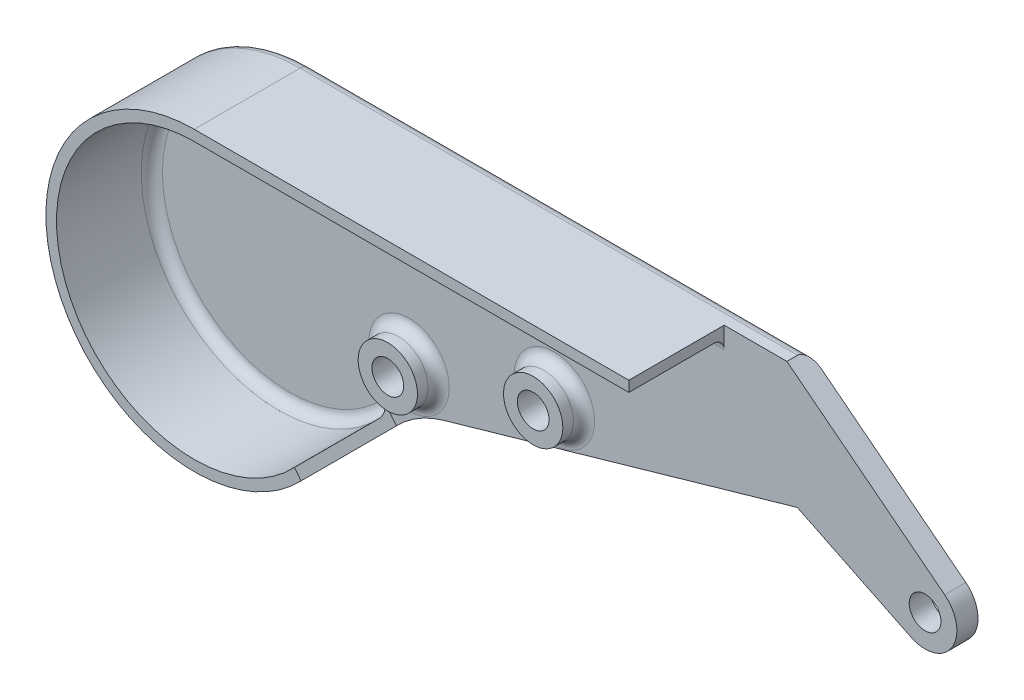
SolidWorks part; units mm, degrees
ref_plane "前视基准面" through (0, 0, 0) normal (0, 0, 1) x (1, 0, 0)
ref_plane "上视基准面" through (0, 0, 0) normal (0, 1, 0) x (1, 0, 0)
ref_plane "右视基准面" through (0, 0, 0) normal (1, 0, 0) x (0, 0, -1)
sketch "Sketch1" plane through (0, 0, 0) normal (0, 0, 1) x (1, 0, 0)
  line L0 (0, 14) -> (46.9536, 14)
  line L1 (46.9536, 14) -> (61.847, 2.364)
  line L2 (4.7883, -13.1557) -> (47.933, 2.5477) construction
  line L3 (47.933, 2.5477) -> (58.6849, -2.6964)
  line L4 (14.5376, -7.0283) -> (47.933, 2.5477)
  arc A0 (0, 14) -> (4.7883, -13.1557) centre (0, 0) ccw
  arc A1 (58.6849, -2.6964) -> (61.847, 2.364) centre (60, 0) ccw
  circle A2 centre (60, 0) radius 1.5
  arc A3 (4.7883, -13.1557) -> (10.0881, -9.7072) centre (0, 0) ccw
  circle A4 centre (0, 0) radius 4.5 construction
  arc A5 (14.5376, -7.0283) -> (10.0881, -9.7072) centre (17.2939, -16.6409) ccw
  dimension "D2" = 6
  dimension "D3" = 28
  dimension "D7" = 3
  dimension "D8" = 9
  dimension "D10" = 10
  dimension "D1" = 60
  dimension "D4" = 38
  dimension "D5" = 20
  dimension "D6" = 12
  dimension "D9" = 16
extrude "Boss-Extrude1" add sketch "Sketch1" along normal blind 2
sketch "Sketch2" plane through (0, 0, 0) normal (0, 0, -1) x (-1, 0, 0)
  line L1 (-46.9536, 14) -> (0, 14) construction
  line L3 (-41.0332, 14) -> (0, 14)
  line L4 (-41.0332, 13) -> (0, 13)
  line L6 (-41.0332, 13) -> (-41.0332, 14)
  line L8 (-10.0881, -9.7072) -> (-43.3043, 10.251) construction
  line L9 (-9.4573, -8.9196) -> (-42.7893, 11.1082) construction
  line L10 (-46.9536, 14) -> (0, 14) construction
  line L11 (-46.9536, 13) -> (0, 13) construction
  line L12 (-10.0881, -9.7072) -> (-9.4573, -8.9196)
  arc A0 (-10.0881, -9.7072) -> (0, 14) centre (0, 0) ccw construction
  arc A1 (-10.0881, -9.7072) -> (0, 14) centre (0, 0) ccw
  arc A2 (-9.4573, -8.9196) -> (0, 13) centre (0, 0) ccw
  dimension "D1" = 1
extrude "Boss-Extrude2" [suppressed] add sketch "Sketch2" along normal blind 9
fillet "Fillet1" [suppressed] radius 1
fillet "Fillet2" [suppressed] radius 1
sketch "Sketch3" plane through (0, 0, 0) normal (0, 0, -1) x (-1, 0, 0)
  line L0 (0, 0) -> (7.0202, 0) construction
  line L1 (-11.2763, -4.1042) -> (0, 0) construction
  circle A0 centre (-11.2763, -4.1042) radius 1.5
  circle A1 centre (-25, 0) radius 1.5
  circle A2 centre (-25, 0) radius 2.8
  circle A3 centre (-11.2763, -4.1042) radius 2.8
  dimension "D1" = 3
  dimension "D2" = 3
  dimension "D5" = 5.6
  dimension "D6" = 5.6
  dimension "D3" = 12
  dimension "D4" = 25
  dimension "D7" = 160
extrude "Boss-Extrude3" [suppressed] add sketch "Sketch3" along normal blind 2
fillet "Fillet3" [suppressed] radius 1
sketch "Sketch4" plane through (0, 0, 0) normal (0, 0, -1) x (-1, 0, 0)
  line L4 (0, 14) -> (-46.9536, 14)
  line L5 (0, 14) -> (-46.9536, 14)
  line L6 (-46.9536, 14) -> (-61.847, 2.364)
  line L7 (-46.9536, 14) -> (-61.847, 2.364)
  line L8 (-58.6849, -2.6964) -> (-47.933, 2.5477)
  line L9 (-58.6849, -2.6964) -> (-47.933, 2.5477)
  line L10 (-47.933, 2.5477) -> (-14.5376, -7.0283)
  line L11 (-47.933, 2.5477) -> (-14.5376, -7.0283)
  arc A1 (-10.0881, -9.7072) -> (0, 14) centre (0, 0) ccw
  circle A4 centre (-11.2763, -4.1042) radius 1.5
  arc A8 (-10.0881, -9.7072) -> (0, 14) centre (0, 0) ccw
  arc A9 (-61.847, 2.364) -> (-58.6849, -2.6964) centre (-60, 0) ccw
  arc A10 (-61.847, 2.364) -> (-58.6849, -2.6964) centre (-60, 0) ccw
  arc A11 (-10.0881, -9.7072) -> (-14.5376, -7.0283) centre (-17.2939, -16.6409) ccw
  arc A12 (-10.0881, -9.7072) -> (-14.5376, -7.0283) centre (-17.2939, -16.6409) ccw
  dimension "D1" = 0
extrude "Cut-Extrude1" [suppressed] cut sketch "Sketch4" against normal blind 4
sketch "草图1" plane through (0, 0, 2) normal (0, 0, 1) x (1, 0, 0)
  line L4 (10.0881, -9.7072) -> (9.4573, -8.9196)
  line L5 (10.0881, -9.7072) -> (9.4573, -8.9196)
  line L9 (0, 13) -> (41.0332, 13)
  line L10 (41.0332, 13) -> (41.0332, 14)
  line L11 (41.0332, 14) -> (0, 14)
  line L15 (0, 13) -> (41.0332, 13)
  line L16 (41.0332, 13) -> (41.0332, 14)
  line L17 (41.0332, 14) -> (0, 14)
  arc A2 (0, 13) -> (9.4573, -8.9196) centre (0, 0) ccw
  arc A3 (0, 14) -> (10.0881, -9.7072) centre (0, 0) ccw
  arc A4 (0, 13) -> (9.4573, -8.9196) centre (0, 0) ccw
  arc A5 (0, 14) -> (10.0881, -9.7072) centre (0, 0) ccw
  dimension "D1" = 0
extrude "凸台-拉伸1" add sketch "草图1" along normal blind 9
fillet "圆角1" radius 1 6 edges at (-12.8822, -5.4818, 0) (20.5166, 13, 2) (23.4768, 14, 0) (-11.9364, -5.15, 2) (31.2353, -2.2403, 0) (12.1359, -8.0738, 0)
sketch "草图2" plane through (0, 0, 2) normal (0, 0, 1) x (1, 0, 0)
  circle A1 centre (11.2763, -4.1042) radius 2.8
  circle A2 centre (11.2763, -4.1042) radius 2.8
  circle A3 centre (25, 0) radius 2.8
  circle A4 centre (25, 0) radius 2.8
  circle A5 centre (25, 0) radius 1.5
  circle A6 centre (25, 0) radius 1.5
  circle A7 centre (11.2763, -4.1042) radius 1.5
  circle A8 centre (11.2763, -4.1042) radius 1.5
  dimension "D1" = 0
  dimension "D2" = 0
  dimension "D3" = 0
  dimension "D4" = 0
extrude "凸台-拉伸2" add sketch "草图2" along normal blind 2
fillet "圆角2" radius 1 2 edges at (27.8, 0, 2) (14.0763, -4.1042, 2)
sketch "草图3" plane through (0, 0, 2) normal (0, 0, 1) x (1, 0, 0)
  circle A1 centre (11.2763, -4.1042) radius 1.5
  circle A2 centre (11.2763, -4.1042) radius 1.5
  circle A3 centre (25, 0) radius 1.5
  circle A4 centre (25, 0) radius 1.5
  dimension "D1" = 0
  dimension "D2" = 0
extrude "切除-拉伸1" cut sketch "草图3" against normal blind 2
